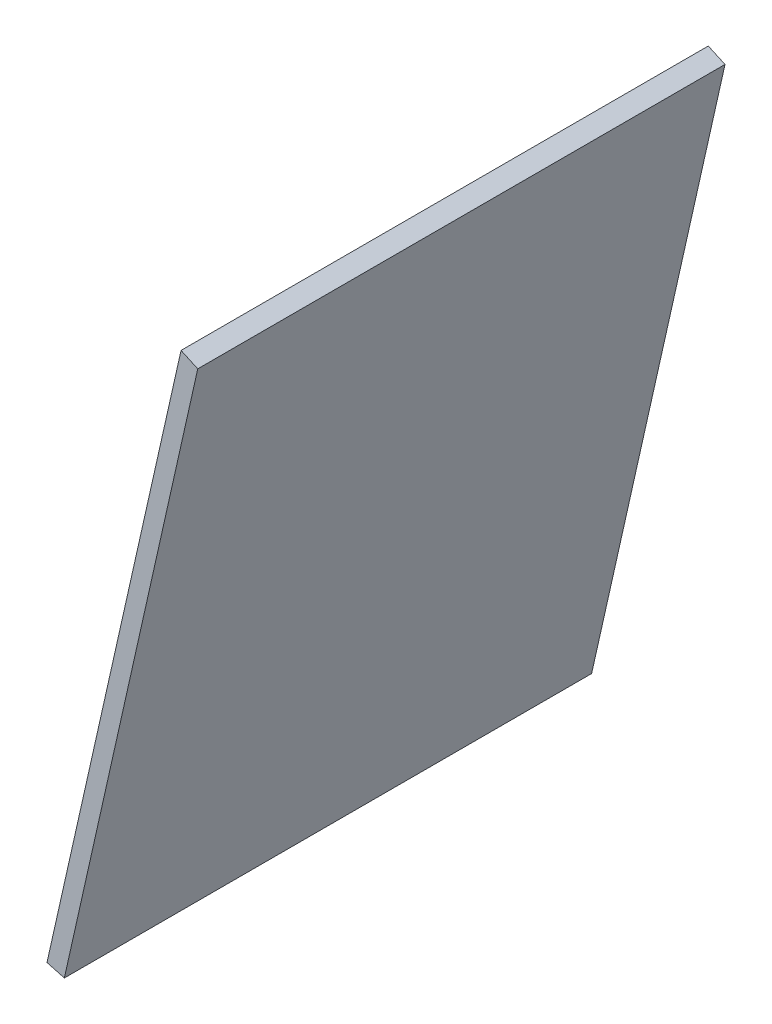
SolidWorks part; units mm, degrees
ref_plane "Front Plane" through (0, 0, 0) normal (0, 0, 1) x (1, 0, 0)
ref_plane "Top Plane" through (0, 0, 0) normal (0, 1, 0) x (1, 0, 0)
ref_plane "Right Plane" through (0, 0, 0) normal (1, 0, 0) x (0, 0, -1)
sketch "Sketch1" plane through (0, 0, 0) normal (0, 0, 1) x (1, 0, 0)
  line L0 (-615.4529, 1612.4067) -> (-756.8391, 982.5955) construction
  line L12 (-596.8655, 1608.234) -> (-738.2517, 978.4228)
  line L13 (-756.6614, 983.3872) -> (-738.2517, 978.4228)
  line L26 (-614.5819, 1616.2869) -> (-596.8655, 1608.234)
  line L63 (-614.5819, 1616.2869) -> (-756.6614, 983.3872)
  dimension "D7" = 19.05
extrude "Boss-Extrude1" add sketch "Sketch1" along normal blind 558.8
